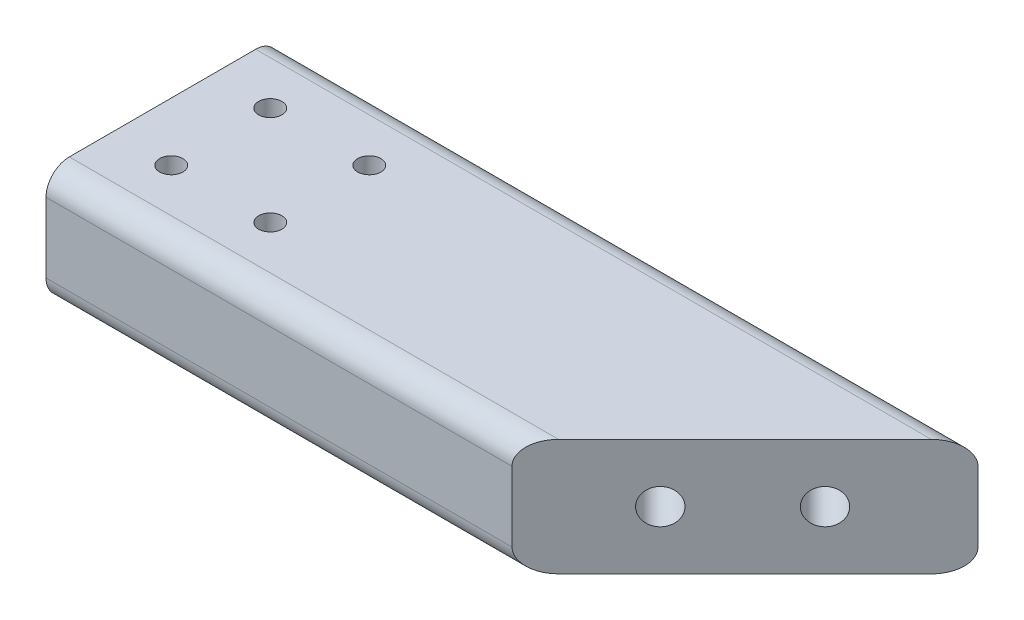
SolidWorks part; units mm, degrees
ref_plane "Front Plane" through (0, 0, 0) normal (0, 0, 1) x (1, 0, 0)
ref_plane "Top Plane" through (0, 0, 0) normal (0, 1, 0) x (1, 0, 0)
ref_plane "Right Plane" through (0, 0, 0) normal (1, 0, 0) x (0, 0, -1)
sketch "Sketch1" plane through (0, 0, 0) normal (0, 1, 0) x (1, 0, 0)
  line L1 (30, -10) -> (-30, -10)
  line L2 (30, -10) -> (30, 10)
  line L3 (30, 10) -> (-30, 10)
  line L4 (-30, -10) -> (-30, 10)
  line L5 (30, -10) -> (-30, 10) construction
  line L6 (30, 10) -> (-30, -10) construction
  point P0 (0, 0)
  dimension "D1" = 60
  dimension "D2" = 20
extrude "Boss-Extrude1" add sketch "Sketch1" along normal blind 10
sketch "Sketch2" plane through (0, 10, 0) normal (0, 1, 0) x (1, 0, 0)
  line L0 (30, 10) -> (-30, 10) construction
  line L2 (-30, 10) -> (-30, -10) construction
  line L7 (-30, -10) -> (30, -10) construction
  circle A0 centre (-25, 4.25) radius 1
  circle A1 centre (-16.5, 4.25) radius 1
  circle A2 centre (-16.5, -4.25) radius 1
  circle A3 centre (-25, -4.25) radius 1
  dimension "D1" = 2
  dimension "D2" = 2
  dimension "D3" = 2
  dimension "D4" = 2
  dimension "D12" = 5.75
  dimension "D5" = 8.5
  dimension "D6" = 8.5
  dimension "D7" = 8.5
  dimension "D8" = 8.5
  dimension "D9" = 5.75
  dimension "D10" = 5
  dimension "D11" = 0
  dimension "D13" = 5.75
extrude "Cut-Extrude1" cut sketch "Sketch2" against normal blind 10
sketch "Sketch5" plane through (0, 10, 0) normal (0, 1, 0) x (1, 0, 0)
  line L0 (10, -10) -> (30, 10)
  line L2 (30, -10) -> (30, 10) construction
  line L3 (10, -10) -> (30, -10)
  line L4 (30, -10) -> (30, 10)
  line L5 (-30, -10) -> (30, -10) construction
  dimension "D1" = 45
  dimension "D2" = 20
  dimension "D3" = 0
extrude "Cut-Extrude4" cut sketch "Sketch5" against normal through all
sketch "Sketch6" plane through (10, 0, 10) normal (0.7071, 0, 0.7071) x (0.7071, 0, -0.7071)
  line L1 (28.2843, 10) -> (0, 10) construction
  line L3 (0, 0) -> (0, 10) construction
  circle A0 centre (19, 5) radius 1.5
  circle A1 centre (9, 5) radius 1.5
  dimension "D1" = 3
  dimension "D2" = 3
  dimension "D3" = 10
  dimension "D4" = 9
  dimension "D5" = 5
extrude "Cut-Extrude5" cut sketch "Sketch6" against normal through all
sketch "Sketch7" plane through (10, 0, 10) normal (0.7071, 0, 0.7071) x (0.7071, 0, -0.7071)
  circle A0 centre (19, 5) radius 3.5
  circle A1 centre (9, 5) radius 3.5
  dimension "D1" = 7
  dimension "D2" = 7
extrude "Cut-Extrude6" cut sketch "Sketch7" against normal through all from offset 5 offset against normal yes
fillet "Fillet2" radius 2 4 edges at (-10, 10, 10) (-10, 0, 10) (0, 0, -10) (0, 10, -10)
